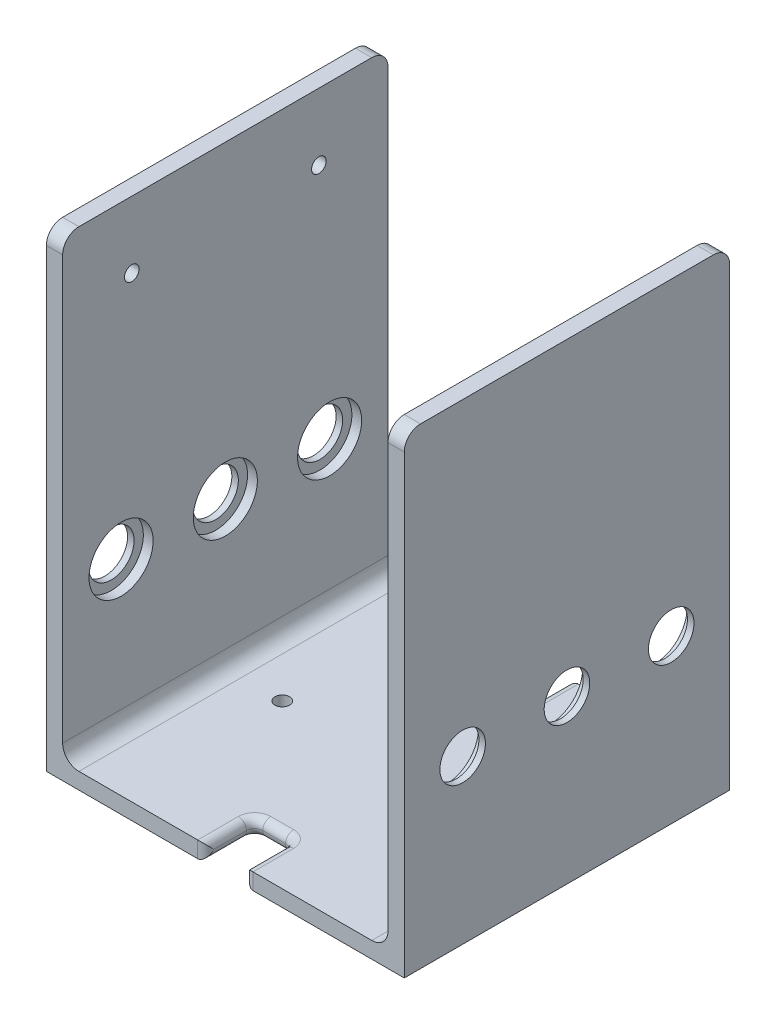
SolidWorks part; units mm, degrees
note: The reader was unsure of these and kept them because the rebuilt part matched: shared geometry of "Sketch4<4>", "Sketch4<6>".
ref_plane "Ön Düzlem" through (0, 0, 0) normal (0, 0, 1) x (1, 0, 0)
ref_plane "Üst Düzlem" through (0, 0, 0) normal (0, 1, 0) x (1, 0, 0)
ref_plane "Sağ Düzlem" through (0, 0, 0) normal (1, 0, 0) x (0, 0, -1)
sketch "Sketch1" plane through (0, 0, 0) normal (0, 0, 1) x (1, 0, 0)
  line L1 (-15.6006, 140) -> (-10.6006, 140)
  line L2 (-15.6006, 140) -> (-15.6006, 0)
  line L3 (-15.6006, 0) -> (-10.6006, 0)
  line L4 (-10.6006, 140) -> (-10.6006, 0)
  line L5 (-15.6006, 140) -> (-10.6006, 0) construction
  line L6 (-15.6006, 0) -> (-10.6006, 140) construction
  line L7 (-15.6006, 0) -> (94.3994, 0)
  line L8 (-15.6006, 0) -> (-15.6006, -5)
  line L9 (-15.6006, -5) -> (94.3994, -5)
  line L10 (94.3994, 0) -> (94.3994, -5)
  line L11 (94.3994, 0) -> (89.3994, 0)
  line L12 (94.3994, 0) -> (94.3994, 140)
  line L13 (94.3994, 140) -> (89.3994, 140)
  line L14 (89.3994, 0) -> (89.3994, 140)
  point P0 (-13.1006, 70)
  dimension "D1" = 5
  dimension "D2" = 140
  dimension "D3" = 5
  dimension "D4" = 110
  dimension "D5" = 5
extrude "Boss-Extrude1" add sketch "Sketch1" against normal blind 100 contours L10 L7 L3 L8 L9 | L14 L7 L12 L13
sketch "Sketch4" plane through (89.3994, 0, 0) normal (-1, 0, 0) x (0, 0, 1)
  line L0 (0, 0) -> (0, 45)
  line L1 (0, 0) -> (0, 140) construction
  line L2 (0, 45) -> (-100, 45)
  line L3 (-100, 0) -> (-100, 140) construction
  line L4 (-50, 45) -> (-82.05, 45)
  line L5 (-50, 45) -> (-17.95, 45)
  circle A0 centre (-50, 45) radius 9.85
  circle A1 centre (-82.05, 45) radius 9.85
  circle A2 centre (-17.95, 45) radius 9.85
  circle A3 centre (-82.05, 45) radius 7
  circle A4 centre (-50, 45) radius 7
  circle A5 centre (-17.95, 45) radius 7
  dimension "D4" = 19.7
  dimension "D5" = 19.7
  dimension "D6" = 19.7
  dimension "D7" = 14
  dimension "D8" = 14
  dimension "D9" = 14
  dimension "D1" = 45
  dimension "D2" = 32.05
  dimension "D3" = 32.05
extrude "Cut-Extrude3" cut sketch "Sketch4" along normal through all both and the other way through all contours L2 A3 L4 | L4 A3 L2 | L2 A4 | L2 A4 | L2 A5 | L2 A5
extrude "Cut-Extrude4" cut sketch "Sketch4<4>" against normal blind 3
sketch "Sketch4<4>" plane through (89.3994, 0, 0) normal (-1, 0, 0) x (0, 0, 1) same geometry as "Sketch4"
extrude "Cut-Extrude5" cut sketch "Sketch4<6>" along normal blind 103
sketch "Sketch4<6>" plane through (89.3994, 0, 0) normal (-1, 0, 0) x (0, 0, 1) same geometry as "Sketch4"
sketch "Sketch5" plane through (-15.6006, 0, 0) normal (-1, 0, 0) x (0, 0, 1)
  line L0 (0, 140) -> (0, 119.5)
  line L1 (0, 140) -> (0, -5) construction
  line L2 (0, 119.5) -> (-21.25, 119.5)
  line L3 (-100, 140) -> (-100, 119.5)
  line L4 (-100, 140) -> (-100, -5) construction
  line L5 (-100, 119.5) -> (-78.75, 119.5)
  circle A0 centre (-78.75, 119.5) radius 2.25
  circle A1 centre (-21.25, 119.5) radius 2.25
  dimension "D4" = 4.5
  dimension "D5" = 4.5
  dimension "D1" = 20.5
  dimension "D2" = 21.25
  dimension "D3" = 21.25
extrude "Cut-Extrude6" cut sketch "Sketch5" against normal up to next and the other way through all
sketch "Sketch6" plane through (0, -5, 0) normal (0, -1, 0) x (1, 0, 0)
  line L0 (39.3994, -50) -> (71.8994, -50)
  line L1 (39.3994, -50) -> (6.8994, -50)
  circle A0 centre (71.8994, -50) radius 2.25
  circle A1 centre (6.8994, -50) radius 2.25
  dimension "D3" = 4.5
  dimension "D4" = 4.5
  dimension "D1" = 32.5
  dimension "D2" = 32.5
extrude "Cut-Extrude7" cut sketch "Sketch6" against normal up to next
sketch "Sketch7" plane through (0, 0, 0) normal (0, 1, 0) x (1, 0, 0)
  line L0 (39.3994, 100) -> (33.3994, 100)
  line L1 (-10.6006, 100) -> (89.3994, 100) construction
  line L2 (33.3994, 100) -> (45.3994, 100)
  line L3 (9.1494, 50) -> (69.6494, 50)
  line L4 (33.3994, 100) -> (45.3994, 100)
  line L5 (33.3994, 100) -> (33.3994, 85)
  line L6 (33.3994, 85) -> (45.3994, 85)
  line L7 (45.3994, 100) -> (45.3994, 85)
  line L8 (33.3994, 0) -> (45.3994, 0)
  line L9 (33.3994, 15) -> (45.3994, 15)
  line L10 (45.3994, 0) -> (45.3994, 15)
  line L11 (33.3994, 0) -> (33.3994, 15)
  circle A0 centre (6.8994, 50) radius 2.25 construction
  circle A1 centre (71.8994, 50) radius 2.25 construction
  line M10 (-10.6006, 0) -> (89.3994, 0)
  line M12 (89.3994, 100) -> (-10.6006, 100)
  dimension "D1" = 6
  dimension "D2" = 12
  dimension "D3" = 15
extrude "Cut-Extrude8" cut sketch "Sketch7" against normal through all contours L7 L5 L6 M12 | L11 L10 L9 M10
fillet "Fillet3" radius 2.5 8 edges at (45.3994, -2.5, 0) (45.3994, -5, -7.5) (45.3994, 0, -7.5) (39.3994, -5, -15) (39.3994, 0, -15) (33.3994, -5, -7.5) (33.3994, -2.5, 0) (33.3994, 0, -7.5)
fillet "Fillet4" radius 2.5 8 edges at (33.3994, -2.5, -100) (33.3994, -5, -92.5) (33.3994, 0, -92.5) (39.3994, -5, -85) (39.3994, 0, -85) (45.3994, -5, -92.5) (45.3994, -2.5, -100) (45.3994, 0, -92.5)
fillet "Fillet5" radius 5 2 edges at (89.3994, 0, -50) (-10.6006, 0, -50)
fillet "Fillet6" radius 5 4 edges at (-13.1006, 140, -100) (-13.1006, 140, 0) (91.8994, 140, -100) (91.8994, 140, 0)
